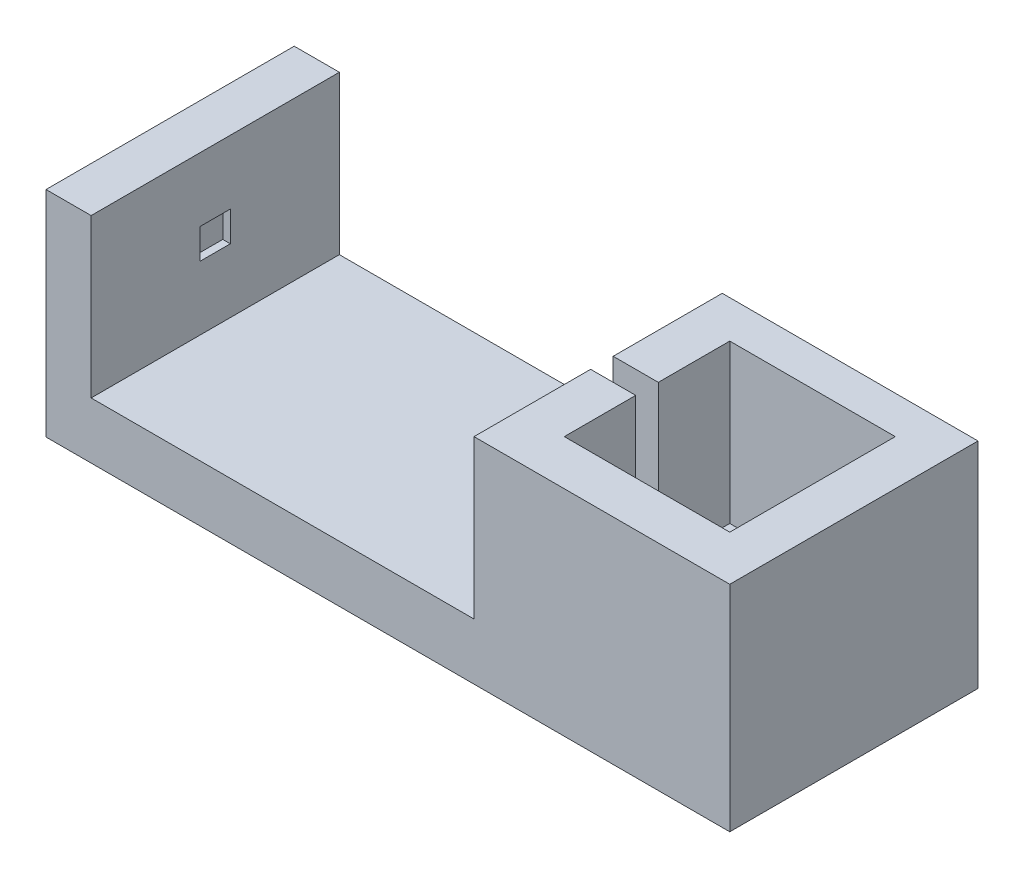
SolidWorks part; units mm, degrees
ref_plane "Front Plane" through (0, 0, 0) normal (0, 0, 1) x (1, 0, 0)
ref_plane "Top Plane" through (0, 0, 0) normal (0, 1, 0) x (1, 0, 0)
ref_plane "Right Plane" through (0, 0, 0) normal (1, 0, 0) x (0, 0, -1)
sketch "Sketch2" plane through (0, 0, 0) normal (0, 0, 1) x (1, 0, 0)
  line L0 (0, 0) -> (12, 0)
  line L2 (12, -42) -> (113.8, -42)
  line L3 (113.8, -42) -> (113.8, 0)
  line L4 (113.8, 0) -> (125.8, 0)
  line L5 (125.8, 0) -> (125.8, -42)
  line L6 (125.8, -42) -> (169.8, -42)
  line L7 (169.8, -42) -> (169.8, 0)
  line L8 (169.8, 0) -> (181.8, 0)
  line L9 (181.8, 0) -> (181.8, -57)
  line L10 (181.8, -57) -> (0, -57)
  line L11 (0, -57) -> (0, 0)
  line L17 (12, 0) -> (12, -42)
  dimension "D1" = 42
  dimension "D2" = 12
  dimension "D3" = 15
  dimension "D4" = 101.8
  dimension "D5" = 44
extrude "Boss-Extrude1" add sketch "Sketch2" against normal blind 66
sketch "Sketch3" plane through (0, 0, 0) normal (0, 0, 1) x (1, 0, 0)
  line L2 (12, -42) -> (12, 0) construction
  line L3 (12, -17) -> (10, -17)
  line L4 (10, -17) -> (10, -25)
  line L5 (10, -25) -> (12, -25)
  line L6 (12, -25) -> (12, -17)
  dimension "D1" = 8
  dimension "D2" = 2
  dimension "D3" = 17
extrude "Cut-Extrude1" cut sketch "Sketch3" against normal blind 37
extrude "Boss-Extrude2" add sketch "Sketch3<3>" against normal blind 29
sketch "Sketch3<3>" plane through (0, 0, 0) normal (0, 0, 1) x (1, 0, 0) same geometry as "Sketch3"
sketch "Sketch4" plane through (125.8, 0, 0) normal (1, 0, 0) x (0, 0, -1)
  line L0 (0, 0) -> (12, 0)
  line L1 (66, 0) -> (0, 0) construction
  line L2 (12, 0) -> (12, -42)
  line L3 (12, -42) -> (0, -42)
  line L4 (0, -42) -> (0, 0)
  line L5 (66, 0) -> (66, -42)
  line L6 (66, -57) -> (66, 0) construction
  line L7 (66, -42) -> (56, -42)
  line L8 (56, -42) -> (56, 0)
  line L9 (56, 0) -> (66, 0)
  dimension "D1" = 12
  dimension "D2" = 44
extrude "Boss-Extrude3" add sketch "Sketch4" along normal up to next
sketch "Sketch5" plane through (0, 0, 0) normal (0, 1, 0) x (1, 0, 0)
  line L1 (113.8, 66) -> (113.8, 0) construction
  line L2 (113.8, 37) -> (125.8, 37)
  line L3 (125.8, 56) -> (125.8, 12) construction
  line L4 (125.8, 37) -> (125.8, 31)
  line L5 (125.8, 31) -> (113.8, 31)
  line L6 (113.8, 66) -> (113.8, 0) construction
  line L7 (113.8, 31) -> (113.8, 37)
  dimension "D1" = 31
  dimension "D2" = 6
extrude "Cut-Extrude2" cut sketch "Sketch5" against normal blind 25
